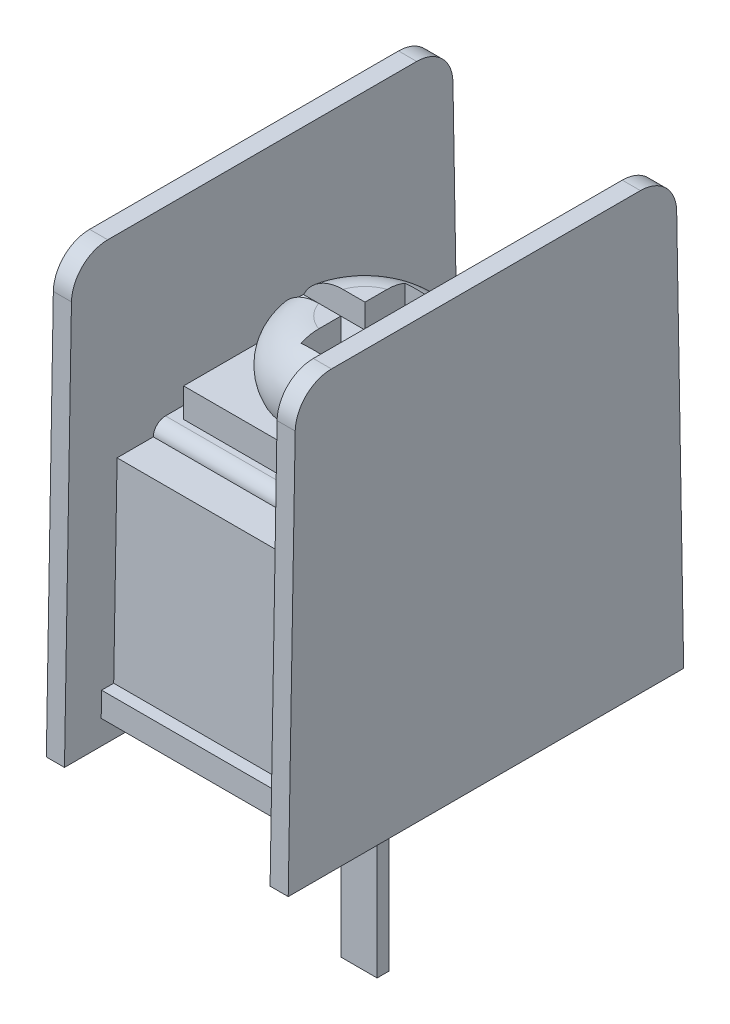
SolidWorks part; units mm, degrees
ref_plane "前视基准面" through (0, 0, 0) normal (0, 0, 1) x (1, 0, 0)
ref_plane "上视基准面" through (0, 0, 0) normal (0, 1, 0) x (1, 0, 0)
ref_plane "右视基准面" through (0, 0, 0) normal (1, 0, 0) x (0, 0, -1)
sketch "草图1" plane through (0, 0, 0) normal (0, 1, 0) x (1, 0, 0)
  line L0 (0, 14.1902) -> (0, -10.6155) construction
  line L1 (-22.4154, 0) -> (19.6333, 0) construction
  line L3 (-5, 8) -> (5, 8)
  line L4 (-5, 8) -> (-5, -8)
  line L5 (-5, -8) -> (5, -8)
  line L6 (5, 8) -> (5, -8)
  dimension "D1" = 10
  dimension "D2" = 16
extrude "拉伸1" add sketch "草图1" along normal blind 18
sketch "草图2" plane through (0, 18, 0) normal (0, 1, 0) x (-1, 0, 0)
  line L1 (5, 8) -> (-5, 8) construction
  line L2 (-4.25, 8) -> (4.25, 8)
  line L3 (-4.25, 8) -> (-4.25, -8)
  line L4 (-4.25, -8) -> (4.25, -8)
  line L8 (4.25, 8) -> (4.25, -8)
  line L9 (-5, -8) -> (5, -8) construction
  line L10 (5, -8) -> (5, 8) construction
  line L11 (-5, 8) -> (-5, -8) construction
  dimension "D1" = 0.75
  dimension "D2" = 0.75
extrude "切除-拉伸1" cut sketch "草图2" against normal blind 8
sketch "草图5" plane through (0, 0, -8) normal (0, 0, -1) x (-1, 0, 0)
  line L0 (-5, 0) -> (5, 0) construction
  line L1 (-4.25, 10) -> (4.25, 10)
  line L2 (-4.25, 10) -> (-4.25, 2)
  line L3 (-4.25, 2) -> (4.25, 2)
  line L4 (4.25, 10) -> (4.25, 2)
  dimension "D1" = 2
extrude "切除-拉伸4" cut sketch "草图5" against normal blind 2
sketch "草图6" plane through (0, 0, -8) normal (0, 0, -1) x (-1, 0, 0)
  line L0 (-5, 0) -> (5, 0) construction
  line L1 (-4.25, 2) -> (4.25, 2)
  line L2 (-4.25, 2) -> (-4.25, 0)
  line L3 (-4.25, 0) -> (4.25, 0)
  line L4 (4.25, 2) -> (4.25, 0)
extrude "切除-拉伸5" cut sketch "草图6" against normal blind 1.5
mirror "镜向3" about plane through (0, 0, 0) normal (0, 0, 1) of "切除-拉伸4", "切除-拉伸5"
draft "拔模1" type of draft neutral plane draft angle 1 faces to draft 8 face at (4.625, 9, 8) face at (-4.625, 9, 8) face at (0, 1, 6.5) face at (0, 6, 6) face at (0, 1, -6.5) face at (-4.625, 9, -8) face at (0, 6, -6) face at (4.625, 9, -8) neutral plane through (4.25, 10, -8) neutral plane normal (0, 1, 0) parameters "D1"=1
sketch "草图7" plane through (0, 0, 0) normal (0, -1, 0) x (1, 0, 0)
  line L1 (4.25, 6.6746) -> (-4.25, 6.6746)
  line L2 (4.25, 6.6746) -> (4.25, -6.6746)
  line L3 (4.25, -6.6746) -> (-4.25, -6.6746)
  line L4 (-4.25, 6.6746) -> (-4.25, -6.6746)
extrude "切除-拉伸6" cut sketch "草图7" against normal blind 1
fillet "圆角1" radius 1.5 4 edges at (4.625, 18, 7.8604) (-4.625, 18, 7.8604) (-4.625, 18, -7.8604) (4.625, 18, -7.8604)
sketch "草图8" plane through (0, 10, 0) normal (0, 1, 0) x (-1, 0, 0)
  line L0 (-4.25, 6) -> (-4.25, -6) construction
  line L1 (-4.25, -4.5) -> (4.25, -4.5)
  line L2 (-4.25, -4.5) -> (-4.25, 4.5)
  line L3 (-4.25, 4.5) -> (4.25, 4.5)
  line L4 (4.25, -4.5) -> (4.25, 4.5)
  line L5 (4.25, -6.3863) -> (4.25, 6.3863) construction
  line L6 (5.894, 0) -> (-6.1893, 0) construction
  dimension "D1" = 9
extrude "拉伸2" add sketch "草图8" along normal blind 0.5
sketch "草图9" plane through (0, 1, 0) normal (0, -1, 0) x (1, 0, 0)
  line L1 (-0.75, 0.25) -> (0.75, 0.25)
  line L2 (-0.75, 0.25) -> (-0.75, -0.25)
  line L3 (-0.75, -0.25) -> (0.75, -0.25)
  line L4 (0.75, 0.25) -> (0.75, -0.25)
  line L5 (-0.75, 0.25) -> (0.75, -0.25) construction
  line L6 (-0.75, -0.25) -> (0.75, 0.25) construction
  point P0 (0, 0)
  dimension "D1" = 1.5
  dimension "D2" = 0.5
extrude "拉伸3" add sketch "草图9" along normal blind 10
fillet "圆角2" radius 0.5 2 edges at (0, 10.5, -4.5) (0, 10.5, 4.5)
sketch "草图10" plane through (0, 10.5, 0) normal (0, 1, 0) x (-1, 0, 0)
  line L1 (0, 8.0097) -> (0, -7.6912) construction
  line L2 (-3.75, 3.75) -> (3.75, 3.75)
  line L3 (-3.75, 3.75) -> (-3.75, -3.75)
  line L4 (-3.75, -3.75) -> (3.75, -3.75)
  line L6 (-6.3124, 0) -> (6.1893, 0) construction
  line L7 (3.75, 3.75) -> (3.75, -3.75)
  dimension "D1" = 7.5
  dimension "D2" = 7.5
extrude "拉伸4" add sketch "草图10" along normal blind 1.2
sketch "草图11" plane through (0, 0, 0) normal (0, 0, 1) x (1, 0, 0)
  line L0 (0, 11.7) -> (0, 14.2)
  line L1 (-3.75, 11.7) -> (3.75, 11.7) construction
  line L2 (0, 14.2) -> (1.5, 14.2)
  line L4 (3.0811, 11.7) -> (0, 11.7)
  line L5 (0, 11.7) -> (-0.0123, 11.7367)
  arc A0 (1.5, 14.2) -> (3.0811, 11.7) centre (1.5, 12.45) cw
  point P9 (3.1156, 11.7)
  point P10 (-0.0123, 14.7322)
  dimension "D1" = 3.25
  dimension "D2" = 1.5
  dimension "D3" = 2.5
revolve "旋转1" add sketch "草图11" angle 360 about L0
sketch "草图12" plane through (0, 14.2, 0) normal (0, 1, 0) x (1, 0, 0)
  line L0 (-3.75, 3.75) -> (-3.75, -3.75) construction
  line L1 (-3.75, 0.5) -> (-0.5, 0.5)
  line L2 (-3.75, 0.5) -> (-3.75, -0.5)
  line L3 (-3.75, -0.5) -> (-0.5, -0.5)
  line L4 (3.75, 0.5) -> (3.75, -0.5)
  line L5 (3.75, -3.75) -> (3.75, 3.75) construction
  line L6 (-3.25, 0) -> (3.25, 0) construction
  line L7 (0, -2.15) -> (0, 2.15) construction
  line L8 (0.5, -2.15) -> (0.5, -0.5)
  line L9 (-0.5, -2.15) -> (-0.5, -0.5)
  line L10 (-0.5, 2.15) -> (0.5, 2.15)
  line L11 (-0.5, -2.15) -> (0.5, -2.15)
  line L12 (-0.5, 0.5) -> (-0.5, 2.15)
  line L13 (-0.5, -2.15) -> (-0.5, 2.15) construction
  line L14 (0.5, 0.5) -> (3.75, 0.5)
  line L15 (0.5, 0.5) -> (0.5, 2.15)
  line L16 (0.5, -2.15) -> (0.5, 2.15) construction
  line L17 (0.5, -0.5) -> (3.75, -0.5)
  circle A0 centre (0, 0) radius 3.25 construction
  point P15 (0, 0)
  point P19 (0, 0)
  dimension "D3" = 0.5
  dimension "D4" = 4.3
  dimension "D1" = 0.5
extrude "切除-拉伸7" cut sketch "草图12" against normal blind 1
